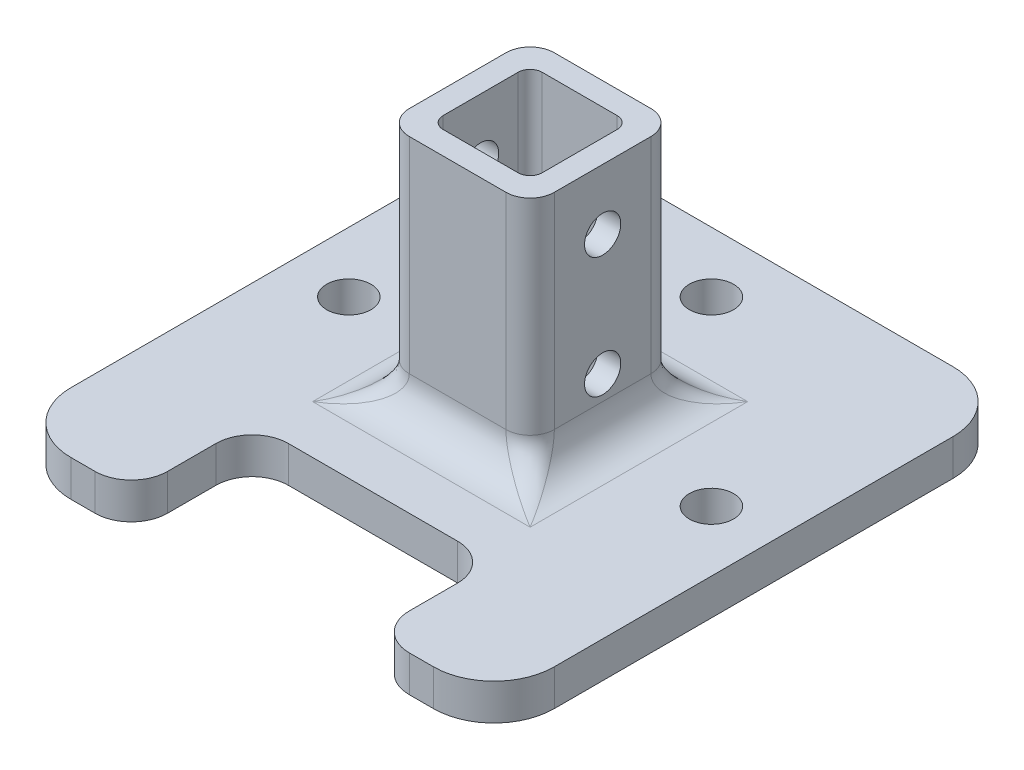
SolidWorks part; units mm, degrees
ref_plane "前视基准面" through (0, 0, 0) normal (0, 0, 1) x (1, 0, 0)
ref_plane "上视基准面" through (0, 0, 0) normal (0, 1, 0) x (1, 0, 0)
ref_plane "右视基准面" through (0, 0, 0) normal (1, 0, 0) x (0, 0, -1)
sketch "草图1" plane through (0, 0, 0) normal (0, 1, 0) x (1, 0, 0)
  line L0 (0, 0) -> (0, 22.885) construction
  line L1 (0, 0) -> (-22.885, 0) construction
  line L3 (-20, -23) -> (20, -23)
  line L4 (-20, -23) -> (-20, 20)
  line L5 (-20, 20) -> (20, 20)
  line L6 (20, -23) -> (20, 20)
  circle A1 centre (0, 15) radius 1.8308
  circle A2 centre (-15, 0) radius 1.8308
  circle A3 centre (0, -15) radius 1.8308
  circle A4 centre (15, 0) radius 1.8308
  dimension "D1" = 15
  dimension "D2" = 15
  dimension "D3" = 43
  dimension "D4" = 40
  dimension "D5" = 20
  dimension "D6" = 23
extrude "凸台-拉伸1" add sketch "草图1" along normal blind 3
sketch "草图3" plane through (0, 0, 23) normal (0, 0, 1) x (1, 0, 0)
  line L0 (-20, 3) -> (20, 3) construction
  line L2 (-16, 3) -> (-16, 33)
  line L3 (-16, 33) -> (16, 33)
  line L4 (16, 3) -> (16, 33)
  line L5 (-20, 3) -> (-20, 0) construction
  line L6 (0, 33) -> (0, 0) construction
  line L7 (-20, 0) -> (20, 0) construction
  line L8 (-16, 0) -> (16, 0)
  line L9 (-16, 0) -> (-16, 3)
  line L11 (16, 0) -> (16, 3)
  circle A0 centre (-11.5, 30) radius 1.5
  circle A1 centre (-11.5, 25) radius 1.5
  circle A2 centre (-11.5, 20) radius 1.5
  circle A3 centre (-11.5, 15) radius 1.5
  circle A4 centre (-11.5, 10) radius 1.5
  circle A6 centre (11.5, 10) radius 1.5
  circle A7 centre (11.5, 15) radius 1.5
  circle A8 centre (11.5, 20) radius 1.5
  circle A9 centre (11.5, 25) radius 1.5
  circle A10 centre (11.5, 30) radius 1.5
  circle A12 centre (-11.5, 5) radius 1.5 [skipped]
  dimension "D4" = 11.5
  dimension "D7" = 3
  dimension "D1" = 30
  dimension "D2" = 32
  dimension "D3" = 4
  dimension "D5" = 6
  dimension "D6" = 3
fillet "圆角2" radius 5 4 edges at (-20, 1.5, -20) (-20, 1.5, 23) (20, 1.5, -20) (20, 1.5, 23)
sketch "草图4" plane through (0, 3, 0) normal (0, 1, 0) x (1, 0, 0)
  line L0 (0, 0) -> (-18.5355, 18.5355) construction
  line L1 (0, 0) -> (18.5355, 18.5355) construction
  line L2 (0, 0) -> (0, 20) construction
  line L3 (-20, 0) -> (20.3639, 0) construction
  line L5 (-4.1, -4.1) -> (4.1, -4.1)
  line L6 (-4.1, -4.1) -> (-4.1, 4.1)
  line L7 (-4.1, 4.1) -> (4.1, 4.1)
  line L8 (4.1, -4.1) -> (4.1, 4.1)
  line L9 (-6, -6) -> (6, -6)
  line L10 (-6, -6) -> (-6, 6)
  line L11 (-6, 6) -> (6, 6)
  line L12 (6, -6) -> (6, 6)
  circle A2 centre (0, 0) radius 20 construction
  dimension "D1" = 12
  dimension "D2" = 8.2
  dimension "D3" = 6
  dimension "D4" = 4.1
extrude "凸台-拉伸3" add sketch "草图4" along normal blind 20
sketch "草图5" plane through (0, 0, 0) normal (1, 0, 0) x (0, 0, -1)
  line L3 (0, 0) -> (0, 28.3702) construction
  circle A4 centre (0, 18) radius 1.5
  circle A5 centre (0, 8) radius 1.5
extrude "切除-拉伸1" cut sketch "草图5" against normal through all and the other way through all
sketch "草图6" plane through (0, 3, 0) normal (0, 1, 0) x (1, 0, 0)
  line L0 (-16, -23) -> (16, -23) construction
  line L1 (-10, -23) -> (10, -23)
  line L2 (-10, -23) -> (-10, -13)
  line L3 (-10, -13) -> (10, -13)
  line L4 (10, -23) -> (10, -13)
  line L5 (-20, 15) -> (-20, -18) construction
  dimension "D1" = 10
  dimension "D2" = 10
  dimension "D3" = 20
extrude "切除-拉伸2" cut sketch "草图6" against normal blind 10
fillet "圆角5" radius 3 8 edges at (6, 3, 0) (0, 3, -6) (-6, 3, 0) (0, 3, 6) (10, 1.5, 13) (10, 1.5, 23) (-10, 1.5, 13) (-10, 1.5, 23)
fillet "圆角6" radius 2 8 edges at (-6.8787, 3.8787, 6.8787) (-6.8787, 3.8787, -6.8787) (6.8787, 3.8787, -6.8787) (6.8787, 3.8787, 6.8787) (-6, 14.5, 6) (-6, 14.5, -6) (6, 14.5, -6) (6, 14.5, 6)
fillet "圆角7" radius 1 4 edges at (4.1, 13, 4.1) (4.1, 13, -4.1) (-4.1, 13, 4.1) (-4.1, 13, -4.1)
